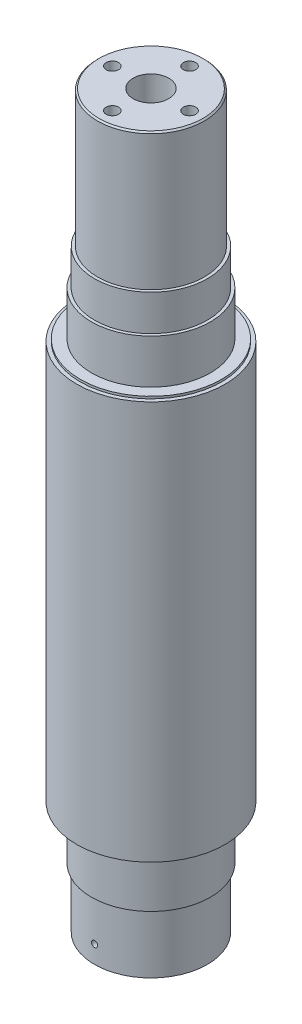
SolidWorks part; units mm, degrees
material "Stainless Steel (ferritic)"
ref_plane "Front" through (0, 0, 0) normal (0, 0, 1) x (1, 0, 0)
ref_plane "Top" through (0, 0, 0) normal (0, 1, 0) x (1, 0, 0)
ref_plane "Right" through (0, 0, 0) normal (1, 0, 0) x (0, 0, -1)
sketch "Sketch1" plane through (0, 0, 0) normal (0, 1, 0) x (1, 0, 0)
  circle A0 centre (0, 0) radius 25
  dimension "D1" = 50
extrude "Boss-Extrude1" add sketch "Sketch1" along normal blind 95 and the other way blind 105
sketch "Sketch2" plane through (0, 95, 0) normal (0, 1, 0) x (1, 0, 0)
  circle A0 centre (0, 0) radius 18
  dimension "D1" = 36
extrude "Boss-Extrude2" add sketch "Sketch2" along normal blind 46
ref_plane "Plane1" through (0, 0, -15) normal (0, 0, 1) x (1, 0, 0)
sketch "Sketch8" plane through (0, 0, -15) normal (0, 0, 1) x (1, 0, 0)
  line L0 (0, 122) -> (0, 103) construction
  line L1 (3, 122) -> (3, 103)
  line L2 (-3, 122) -> (-3, 103)
  line L4 (25, 95) -> (-25, 95) construction
  arc A0 (3, 122) -> (-3, 122) centre (0, 122) ccw
  arc A1 (-3, 103) -> (3, 103) centre (0, 103) ccw
  point P2 (0, 112.5)
  dimension "D2" = 3
  dimension "D1" = 17.5
  dimension "D3" = 9.5
extrude "Cut-Extrude1" cut sketch "Sketch8" against normal blind 10
chamfer "Chamfer1" distance 0.5 angle 45 1 edges at (0, 141, 18)
sketch "Sketch9" plane through (0, -105, 0) normal (0, -1, 0) x (1, 0, 0)
  circle A0 centre (0, 0) radius 10
  dimension "D1" = 20
extrude "Cut-Extrude2" cut sketch "Sketch9" against normal blind 30 draft 8
sketch "Sketch10" plane through (0, -105, 0) normal (0, -1, 0) x (1, 0, 0)
  circle A0 centre (0, 0) radius 6.5
  dimension "D1" = 13
extrude "Cut-Extrude3" cut sketch "Sketch10" against normal blind 50
sketch "Sketch11" plane through (0, 141, 0) normal (0, 1, 0) x (1, 0, 0)
  circle A0 centre (0, 0) radius 6
  dimension "D1" = 12
extrude "Cut-Extrude4" cut sketch "Sketch11" against normal through all
hole_wizard "M5x0.8 Tapped Hole1" positions "Sketch13" profile "Sketch15" tap size "M5x0.8" standard "ANSI Metric"
sketch "Sketch13" plane through (0, 141, 0) normal (0, 1, 0) x (1, 0, 0)
  point P0 (0, 13)
  dimension "D1" = 13
sketch "Sketch15" plane through (0, 141, -13) normal (1, 0, 0) x (0, 0, 1)
  line L0 (0, 0) -> (0, 12)
  line L1 (0, 12) -> (2.1, 10.7382)
  line L2 (2.1, 10.7382) -> (2.1, 0)
  line L5 (2.1, 0) -> (0, 0)
  line L10 (0, 12) -> (-2.1, 10.7382) construction
  line L11 (0, -6.35) -> (0, 107.95) construction
  dimension "Tap Drill Dia." = 4.2
  dimension "Tap Drill Depth" = 12
  dimension "Drill Angle" = 118
cosmetic thread "Hole Thread1" parameters "D1"=10, "D2"=5
pattern_circular "CirPattern1" count 4 over 360 about axis through (0, -105, 0) along (0, 1, 0) of "M5x0.8 Tapped Hole1" reverse direction yes
cosmetic thread "Hole Thread2" parameters "D1"=10, "D2"=5
cosmetic thread "Hole Thread3" parameters "D1"=10, "D2"=5
cosmetic thread "Hole Thread4" parameters "D1"=10, "D2"=5
hole_wizard "M2.5x0.45 Tapped Hole1" positions "Sketch19" profile "Sketch20" tap size "M2.5x0.45" standard "ANSI Metric"
sketch "Sketch19" plane through (0, -105, 0) normal (0, -1, 0) x (-1, 0, 0)
  point P0 (-12.2, 0)
  dimension "D1" = 12.2
sketch "Sketch20" plane through (12.2, -105, 0) normal (1, 0, 0) x (0, 0, -1)
  line L0 (0, 0) -> (0, 9.35)
  line L1 (0, 9.35) -> (1.025, 8.7341)
  line L2 (1.025, 8.7341) -> (1.025, 0)
  line L5 (1.025, 0) -> (0, 0)
  line L10 (0, 9.35) -> (-1.025, 8.7341) construction
  line L11 (0, -6.35) -> (0, 107.95) construction
  dimension "Tap Drill Dia." = 2.05
  dimension "Tap Drill Depth" = 9.35
  dimension "Drill Angle" = 118
cosmetic thread "Hole Thread7" parameters "D1"=8, "D2"=2.5
mirror "Mirror2" about plane through (0, 0, 0) normal (1, 0, 0) of "M2.5x0.45 Tapped Hole1"
cosmetic thread "Hole Thread8" parameters "D1"=8, "D2"=2.5
sketch "Sketch21" plane through (0, -1, 0) normal (0, 1, 0) x (1, 0, 0)
  circle A0 centre (0, 0) radius 20
  circle A1 centre (0, 0) radius 25
  dimension "D1" = 40
  dimension "D2" = 50
extrude "Cut-Extrude6" cut sketch "Sketch21" along normal blind 27 from offset 69
extrude "Cut-Extrude7" cut sketch "Sketch21<2>" against normal blind 39 from offset 66 offset against normal yes
sketch "Sketch21<2>" plane through (0, -1, 0) normal (0, 1, 0) x (1, 0, 0) same geometry as "Sketch21"
sketch "Sketch23" plane through (0, 95, 0) normal (0, 1, 0) x (1, 0, 0)
  circle A0 centre (0, 0) radius 25
  circle A1 centre (0, 0) radius 23.75
  dimension "D1" = 47.5
  dimension "D2" = 50
extrude "Cut-Extrude8" cut sketch "Sketch23" against normal blind 0.75 from offset 27 offset against normal yes
sketch "Sketch24" plane through (0, -105, 0) normal (0, -1, 0) x (1, 0, 0)
  circle A0 centre (0, 0) radius 19
  circle A1 centre (0, 0) radius 20
  dimension "D1" = 38
  dimension "D2" = 40
extrude "Cut-Extrude9" cut sketch "Sketch24" against normal blind 20.1
hole_wizard "M2.5x0.45 Tapped Hole2" positions "3DSketch1" profile "Sketch22" tap size "M2.5x0.45" standard "ANSI Metric"
sketch3d "3DSketch1"
  point P0 (0, -99, -19)
  point P2 (0, -99, 19)
  point P3 (0, 0, 0)
  point P7 (0, 0, 0)
  point P8 (0, 0, 0)
  dimension "D1" = 6
  dimension "D2" = 6
sketch "Sketch22" plane through (0, -99, -19) normal (1, 0, 0) x (0, 1, 0)
  line L0 (0, 0) -> (0, 5.6159)
  line L1 (0, 5.6159) -> (1.025, 5)
  line L2 (1.025, 5) -> (1.025, 0)
  line L5 (1.025, 0) -> (0, 0)
  line L10 (0, 5.6159) -> (-1.025, 5) construction
  line L11 (0, -6.35) -> (0, 107.95) construction
  dimension "Tap Drill Dia." = 2.05
  dimension "Tap Drill Depth" = 5
  dimension "Drill Angle" = 118
cosmetic thread "Hole Thread9" parameters "D1"=5, "D2"=2.5
cosmetic thread "Hole Thread10" parameters "D1"=5, "D2"=2.5
sketch "Sketch25" plane through (0, 95, 0) normal (0, 1, 0) x (1, 0, 0)
  circle A0 centre (0, 0) radius 19
  circle A1 centre (0, 0) radius 20
  dimension "D1" = 38
  dimension "D2" = 40
extrude "Cut-Extrude10" cut sketch "Sketch25" against normal blind 12.1
